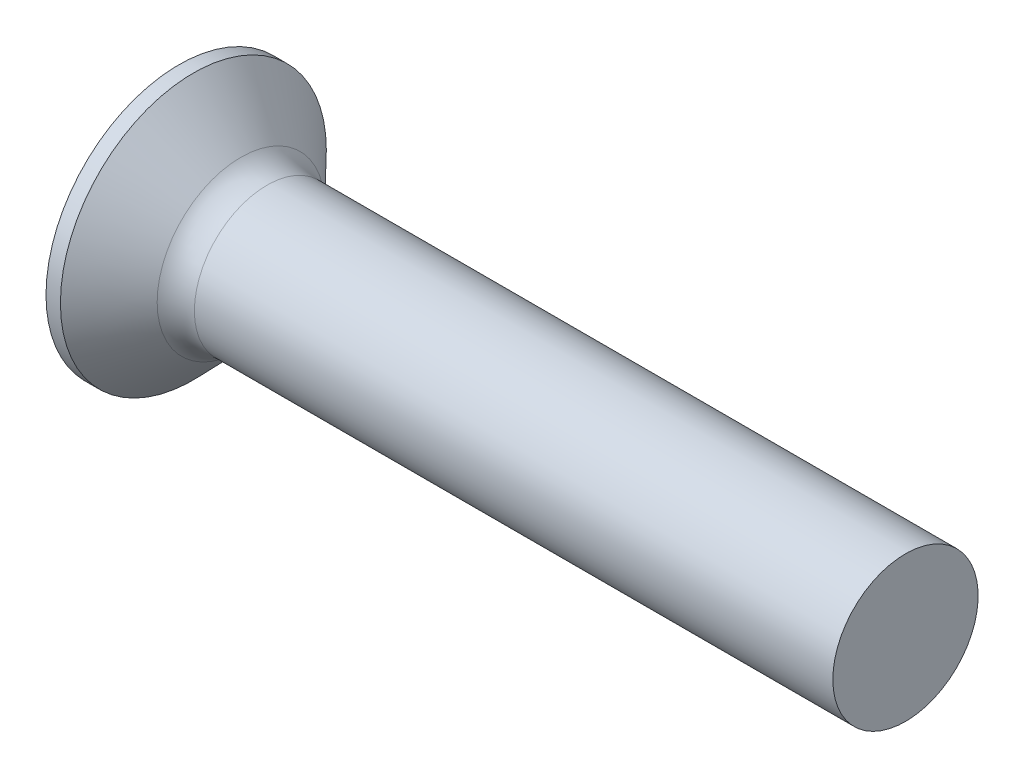
SolidWorks part; units mm, degrees
ref_plane "Plane1" through (0, 0, 0) normal (0, 0, 1) x (1, 0, 0)
ref_plane "Plane2" through (0, 0, 0) normal (0, 1, 0) x (1, 0, 0)
ref_plane "Plane3" through (0, 0, 0) normal (1, 0, 0) x (0, 0, -1)
sketch "BodySke" plane through (0, 0, 0) normal (0, 0, 1) x (1, 0, 0)
  line L0 (0, 0) -> (52.3, 0)
  line L1 (52.3, 0) -> (52.3, 5)
  line L2 (52.3, 5) -> (7.3, 5)
  line L3 (3.2924, -9.15) -> (7.3, -5) construction
  line L4 (-15.875, 0) -> (82.55, 0) construction
  line L5 (3.2924, 9.15) -> (7.3, 5)
  line L6 (8.8, 8.175) -> (8.8, -7.7) construction
  line L7 (2.3, 2.7793) -> (2.3, -13.0957) construction
  line L8 (3.2924, 9.15) -> (2.3, 9.15)
  arc A0 (0, 0) -> (2.3, 9.15) centre (19.3505, 0) cw
  dimension "Diameter" = 10
  dimension "Head_dia" = 18.3
  dimension "Length" = 50
  dimension "Advance" = 1.5
revolve "Base-Revolve" add sketch "BodySke" angle 360 about L4
cosmetic thread "ThreadCosmetic" [suppressed] parameters "Thread_length"=43.5, "Thread_minor"=8.344
fillet "Fillet1" radius 2.5 1 edges at (7.3, 0, 5)
sketch "Sketch3" plane through (0, 0, 0) normal (1, 0, 0) x (0, 0, -1)
  line L0 (1.08, -5.15) -> (-1.08, -5.15)
  line L1 (1.08, -5.15) -> (1.08, 5.15)
  line L2 (-1.08, 5.15) -> (1.08, 5.15)
  line L3 (-1.08, 5.15) -> (-1.08, -5.15)
  dimension "D1" = 1.08
  dimension "D2" = 5.15
ref_plane "Plane4" through (6.05, 0, 0) normal (1, 0, 0) x (0, 0, -1)
sketch "Sketch4" plane through (6.05, 0, 0) normal (1, 0, 0) x (0, 0, -1)
  line L0 (1.08, -2.1336) -> (-1.08, -2.1336)
  line L1 (1.08, -2.1336) -> (1.08, 2.1336)
  line L2 (-1.08, 2.1336) -> (1.08, 2.1336)
  line L3 (-1.08, 2.1336) -> (-1.08, -2.1336)
  dimension "D1" = 2.16
  dimension "D2" = 4.2672
  dimension "D3" = 1.08
  dimension "D4" = 2.1336
loft "Recess" cut profiles "Sketch3", "Sketch4"
pattern_circular "RecPat" count 2 every 90 about axis through (-15.875, 0, 0) along (1, 0, 0) of "Recess"
sketch "RecCorSke" plane through (0, 0, 0) normal (0, 0, 1) x (1, 0, 0)
  line L0 (-3.175, 0) -> (15.875, 0) construction
  line L2 (0, 0) -> (0, 2.3536)
  line L3 (0, 2.3536) -> (6.05, 1.9305)
  line L4 (6.05, 1.9305) -> (6.6773, 0)
  line L5 (6.6773, 0) -> (0, 0)
revolve "RecessCore" cut sketch "RecCorSke" angle 360 about L0
sketch "ThdSchSke" plane through (0, 0, 0) normal (0, 0, 1) x (1, 0, 0)
  line L0 (8.8, -4.172) -> (8.2202, -5)
  line L1 (8.8, -4.172) -> (9.3798, -5)
  line L2 (9.3798, -5) -> (9.3798, -6.25)
  line L3 (-3.175, 0) -> (5.1513, 0) construction
  line L5 (9.3798, -6.25) -> (8.2202, -6.25)
  line L6 (8.2202, -6.25) -> (8.2202, -5)
  dimension "Diameter" = 10
  dimension "Thread_minor" = 8.344
  dimension "Start" = 8.8
revolve "ThreadSchematic" [suppressed] cut sketch "ThdSchSke" angle 360 about L3
pattern_linear "ThdSchPat" [suppressed]
equation "\"D1@Sketch3\" = \"Cross_width@Sketch3\" / 2"
equation "\"D2@Sketch3\" = \"Cross_dia@Sketch3\" / 2"
equation "\"Depth@RecCorSke\" = \"Cross_depth@Plane4\""
equation "\"D1@Sketch4\" = \"Cross_width@Sketch3\""
equation "\"D2@Sketch4\" = \"Cross_dia@Sketch3\" - 2.0 * \"Cross_depth@Plane4\" * tan(26.5  * 0.017453292)"
equation "\"D3@Sketch4\" = \"D1@Sketch4\" / 2"
equation "\"D4@Sketch4\" = \"D2@Sketch4\" / 2"
equation "\"Thread_length@ThreadCosmetic\" = ((sgn( (\"Length@BodySke\" - \"Advance@BodySke\" - \"Side_ht@BodySke\" ) - \"Thread_nom@BodySke\" )-1)*( (\"Length@BodySke\" - \"Advance@BodySke\" - \"Side_ht@BodySke\" ) - \"Thread_nom@BodySke\" ))/-2+ \"Thread_nom@BodySke\""
equation "\"Thread_minor@ThdSchSke\" = \"Thread_minor@ThreadCosmetic\""
equation "\"Diameter@ThdSchSke\" = \"Diameter@BodySke\""
equation "\"Overcut@ThdSchSke\" = \"Diameter@BodySke\" * 1.25"
equation "\"Start@ThdSchSke\" = \"Oval_ht@BodySke\" + \"Length@BodySke\" - \"Thread_length@ThreadCosmetic\"  '---Countersunk---"
equation "\"Num_threads@ThdSchPat\" = int( \"Thread_length@ThreadCosmetic\" / \"Advance@BodySke\" + 0.999 )  + 1"
equation "\"Advance@ThdSchPat\" = \"Thread_length@ThreadCosmetic\" /  (\"Num_threads@ThdSchPat\" - 1) 'relax it"
